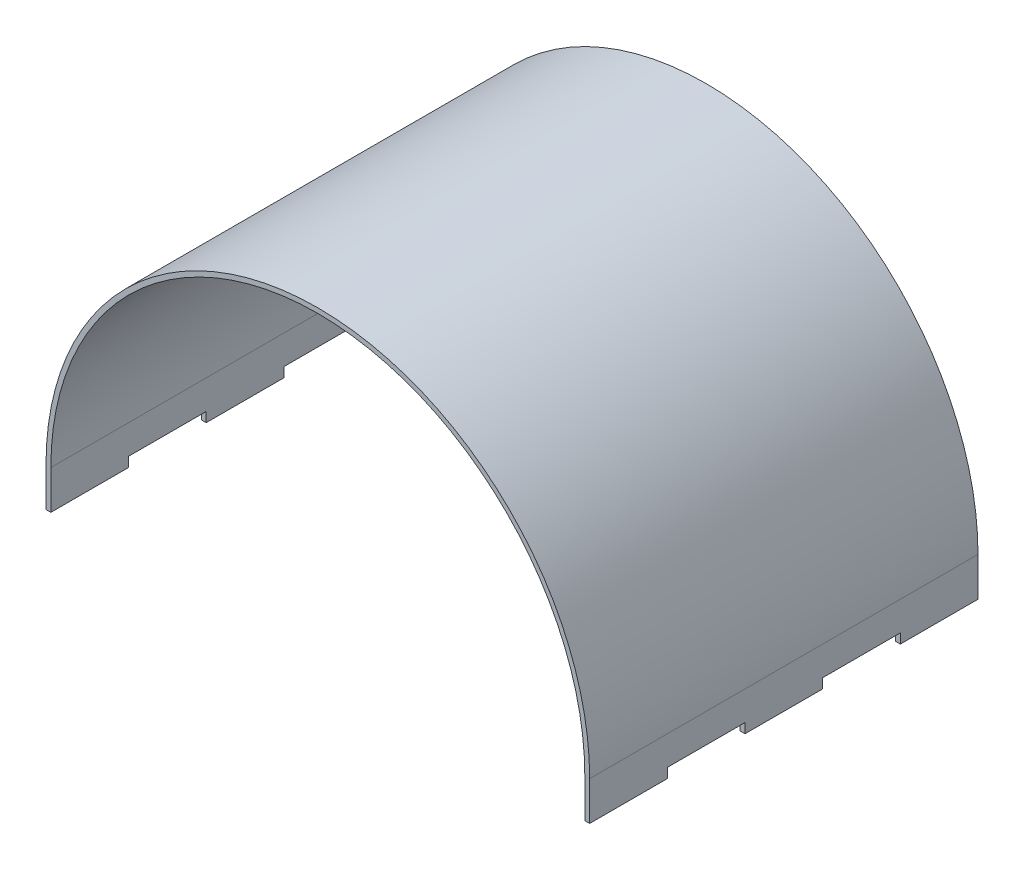
SolidWorks part; units mm, degrees
ref_plane "Front Plane" through (0, 0, 0) normal (0, 0, 1) x (1, 0, 0)
ref_plane "Top Plane" through (0, 0, 0) normal (0, 1, 0) x (1, 0, 0)
ref_plane "Right Plane" through (0, 0, 0) normal (1, 0, 0) x (0, 0, -1)
sketch "Sketch1" plane through (0, 0, 0) normal (0, 0, 1) x (1, 0, 0)
  line L0 (0, 0) -> (3.175, 0)
  line L1 (352.425, 0) -> (355.6, 0)
  line L2 (0, 0) -> (0, 25.4)
  line L3 (3.175, 0) -> (3.175, 25.4)
  line L4 (352.425, 0) -> (352.425, 25.4)
  line L5 (355.6, 0) -> (355.6, 25.4)
  arc A0 (0, 25.4) -> (355.6, 25.4) centre (177.8, 25.4) cw
  arc A1 (352.425, 25.4) -> (3.175, 25.4) centre (177.8, 25.4) ccw
  dimension "D1" = 3.175
  dimension "D2" = 3.175
  dimension "D3" = 355.6
  dimension "D4" = 25.4
  dimension "D5" = 25.4
  dimension "D6" = 25.4
  dimension "D7" = 25.4
extrude "Boss-Extrude1" add sketch "Sketch1" along normal blind 254
sketch "Sketch2" plane through (355.6, 0, 0) normal (1, 0, 0) x (0, 0, -1)
  line L0 (-254, 0) -> (0, 0) construction
  line L1 (-203.2, 0) -> (-152.4, 0)
  line L2 (-203.2, 0) -> (-203.2, 6.35)
  line L3 (-203.2, 6.35) -> (-152.4, 6.35)
  line L4 (-152.4, 0) -> (-152.4, 6.35)
  line L5 (-254, 0) -> (-254, 25.4) construction
  line L6 (-101.6, 0) -> (-50.8, 0)
  line L7 (-101.6, 0) -> (-101.6, 6.35)
  line L8 (-101.6, 6.35) -> (-50.8, 6.35)
  line L9 (-50.8, 0) -> (-50.8, 6.35)
  point P12 (0, 0)
  dimension "D1" = 50.8
  dimension "D2" = 6.35
  dimension "D3" = 50.8
  dimension "D4" = 6.35
  dimension "D5" = 50.8
  dimension "D6" = 50.8
extrude "Cut-Extrude1" cut sketch "Sketch2" against normal through all contours L2 L1 L4 L3 | L7 L6 L9 L8
